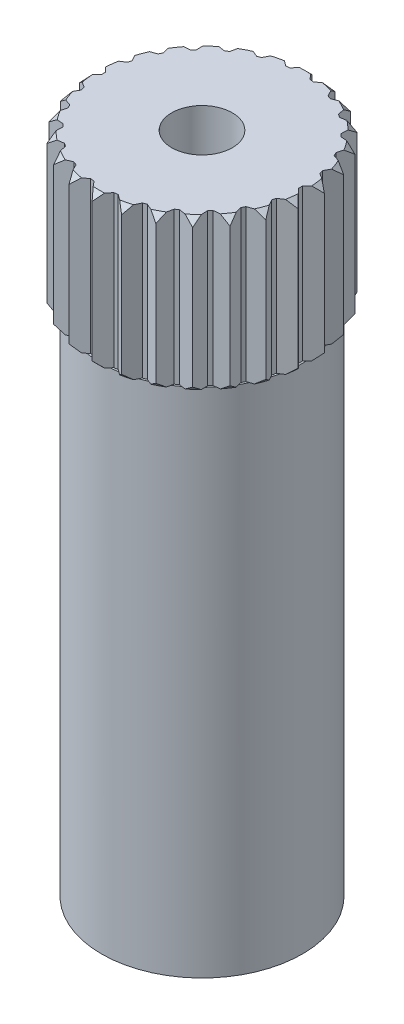
SolidWorks part; units mm, degrees
material "Brass"
ref_plane "Front Plane" through (0, 0, 0) normal (0, 0, 1) x (1, 0, 0)
ref_plane "Top Plane" through (0, 0, 0) normal (0, 1, 0) x (1, 0, 0)
ref_plane "Right Plane" through (0, 0, 0) normal (1, 0, 0) x (0, 0, -1)
sketch "ShaftS" plane through (0, 0, 0) normal (0, 1, 0) x (1, 0, 0)
  circle A0 centre (0, 0) radius 2.9
  dimension "D1" = 5.8
extrude "SHAFT" add sketch "ShaftS" along normal blind 13.5
sketch "ShaftExtensionS" plane through (0, 13.5, 0) normal (0, 1, 0) x (1, 0, 0)
  circle A0 centre (0, 0) radius 2.6
  circle A1 centre (0, 0) radius 2.9 construction
  dimension "D1" = 0.3
extrude "SHAFT EXTENSION" add sketch "ShaftExtensionS" along normal blind 4
sketch "ToothS" plane through (0, 17.5, 0) normal (0, 1, 0) x (1, 0, 0)
  line L0 (0, 2.6) -> (0, 2.9) construction
  line L1 (0, 2.9) -> (-0.2629, 2.5867)
  line L2 (0, 2.9) -> (0.2629, 2.5867)
  line L3 (-0.2629, 2.5867) -> (0.2629, 2.5867) construction
  arc A0 (0.2629, 2.5867) -> (-0.2629, 2.5867) centre (0, 0) ccw
  circle A3 centre (0, 0) radius 2.6 construction
  circle A4 centre (0, 0) radius 2.9 construction
  dimension "D1" = 80
  dimension "D2" = 0.5258
  dimension "D3" = 0.3
extrude "TOOTH" add sketch "ToothS" against normal up to body separate body
pattern_circular "TOOTH CP" count 26 over 360 about axis through (0, 17.5, 0) along (0, -1, 0) of "TOOTH" reverse direction yes
sketch "SmallBoreS" plane through (0, 17.5, 0) normal (0, 1, 0) x (1, 0, 0)
  circle A0 centre (0, 0) radius 0.8
  dimension "D1" = 1.6
extrude "SMALL BORE" cut sketch "SmallBoreS" against normal blind 4
sketch "ShaftUnderCutS" plane through (0, 0, 0) normal (0, 0, 1) x (1, 0, 0)
  line L0 (2.9, 0) -> (2.65, 0)
  line L1 (2.65, 0) -> (2.65, 13.5)
  line L2 (2.65, 13.5) -> (2.9, 13.5)
  line L3 (2.9, 13.5) -> (2.9, 0)
  line L4 (0, 0) -> (2.65, 0) construction
  line L5 (2.7115, 13.5) -> (2.3867, 13.5) construction
  line L6 (0, 13.5) -> (0, 0) construction
  dimension "D1" = 0.25
  dimension "D2" = 2.65
  dimension "D3" = 2.9
revolve "SHAFT UNDER CUT" cut sketch "ShaftUnderCutS" angle 360 about axis through (0, 13.5, 0) along (0, -1, 0)
sketch "TeethChamferS" plane through (0, 0, 0) normal (1, 0, 0) x (0, 0, -1)
  line L0 (2.9, 17.3232) -> (2.9, 17.5)
  line L1 (2.9, 17.5) -> (2.7232, 17.5)
  line L2 (2.7232, 17.5) -> (2.9, 17.3232)
  line L3 (2.9, 13.5) -> (2.9, 17.5) construction
  line L4 (2.9, 15.5) -> (0, 15.5) construction
  line L5 (0, 17.5) -> (0, 13.5) construction
  line L6 (2.7232, 13.5) -> (2.9, 13.6768)
  line L7 (2.9, 13.5) -> (2.7232, 13.5)
  line L8 (2.9, 13.6768) -> (2.9, 13.5)
  point P4 (2.9, 15.5)
  dimension "D1" = 45
  dimension "D2" = 0.25
revolve "TEETH CHAMFER" cut sketch "TeethChamferS" angle 360 about axis through (0, 13.5, 0) along (0, 1, 0)
ref_axis "Axe1" through (0, -42.168, 0) along (0, 1, 0)
